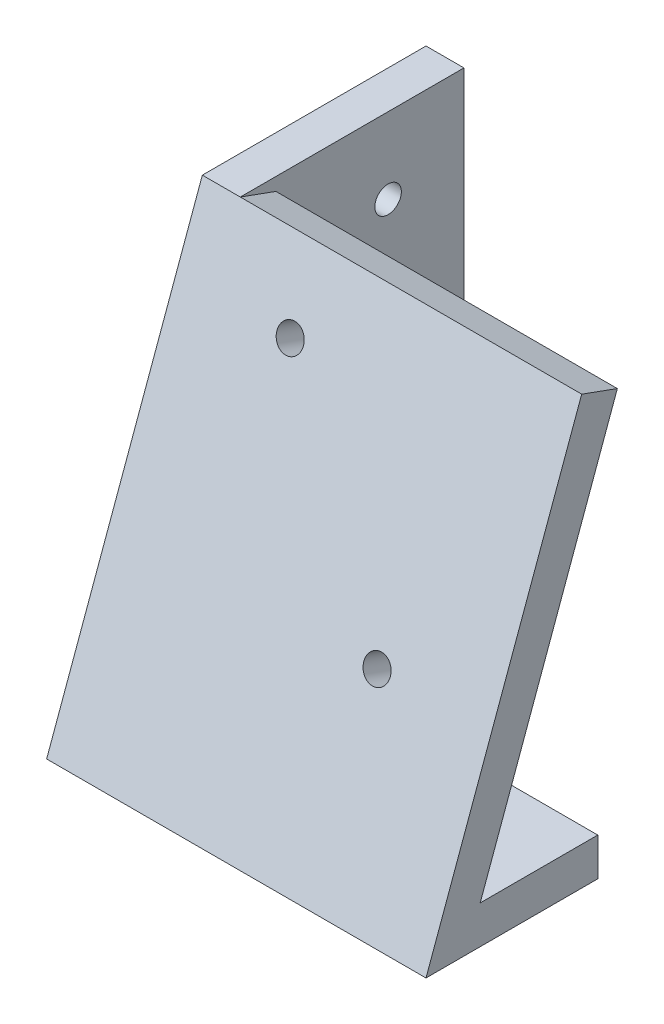
SolidWorks part; units mm, degrees
material "ABS"
ref_plane "Front Plane" through (0, 0, 0) normal (0, 0, 1) x (1, 0, 0)
ref_plane "Top Plane" through (0, 0, 0) normal (0, 1, 0) x (1, 0, 0)
ref_plane "Right Plane" through (0, 0, 0) normal (1, 0, 0) x (0, 0, -1)
sketch "Sketch1" plane through (0, 0, 0) normal (1, 0, 0) x (0, 0, -1)
  line L0 (0, 0) -> (-50, 0)
  line L1 (-50, 0) -> (-29.4788, 56.3816)
  line L2 (-29.4788, 56.3816) -> (-24.7803, 54.6715)
  line L3 (-24.7803, 54.6715) -> (-42.8593, 5)
  line L4 (-42.8593, 5) -> (0, 5)
  line L5 (0, 5) -> (0, 0)
  dimension "D1" = 60
  dimension "D2" = 50
  dimension "D3" = 70
  dimension "D4" = 5
  dimension "D5" = 5
extrude "Main" add sketch "Sketch1" along normal mid plane 50
sketch "Sketch2" plane through (0, 0, 0) normal (0, 0, -1) x (-1, 0, 0)
  line L0 (-25, 56.3816) -> (25, 56.3816) construction
  line L1 (-25, 0) -> (-20, 0)
  line L2 (-25, 0) -> (-25, 56.3816)
  line L3 (-25, 56.3816) -> (-20, 56.3816)
  line L4 (-20, 0) -> (-20, 56.3816)
  dimension "D1" = 5
extrude "Back" add sketch "Sketch2" against normal up to next
hole_wizard "Base Holes" positions "3DSketch4" profile "Sketch5" hole size "Ø3.5" standard "ANSI Metric"
sketch3d "3DSketch4"
  line L0 (-25, 5, 0) -> (-25, 5, 42.8593) construction
  line L4 (20, 5, 42.8593) -> (-25, 5, 42.8593) construction
  point P0 (10, 5, 32.6993)
  point P2 (-10, 5, 32.6993)
  dimension "D1" = 15
  dimension "D2" = 15
  dimension "D3" = 10.16
  dimension "D4" = 10.16
sketch "Sketch5" plane through (10, 5, 32.6993) normal (1, 0, 0) x (0, 0, 1)
  line L0 (0, 0) -> (0, 5)
  line L1 (0, 5) -> (1.75, 5)
  line L2 (1.75, 5) -> (1.75, 0)
  line L5 (1.75, 0) -> (0, 0)
  line L10 (0, 5) -> (-1.75, 5) construction
  line L11 (0, -6.35) -> (0, 107.95) construction
  dimension "Hole Dia." = 3.5
  dimension "Hole Depth" = 5
  dimension "Drill Angle" = 180
hole_wizard "BackPanelHoles" positions "Sketch6" profile "Sketch7" hole size "Ø1.0" standard "ANSI Metric"
sketch "Sketch6" plane through (20, 0, 0) normal (-1, 0, 0) x (0, 0, 1)
  line L0 (29.4788, 56.3816) -> (0, 56.3816) construction
  line L1 (0, 5) -> (0, 56.3816) construction
  line L2 (50, 0) -> (0, 0) construction
  point P0 (10, 46.3816)
  point P2 (25, 20)
  dimension "D1" = 10
  dimension "D2" = 10
  dimension "D3" = 20
  dimension "D4" = 25
sketch "Sketch7" plane through (20, 46.3816, 10) normal (0, 1, 0) x (0, 0, 1)
  line L0 (0, 0) -> (0, 5)
  line L1 (0, 5) -> (1.75, 5)
  line L2 (1.75, 5) -> (1.75, 0)
  line L5 (1.75, 0) -> (0, 0)
  line L10 (0, 5) -> (-1.75, 5) construction
  line L11 (0, -6.35) -> (0, 107.95) construction
  dimension "Hole Dia." = 3.5
  dimension "Hole Depth" = 5
  dimension "Drill Angle" = 180
hole_wizard "Ø1.0mm Dowel Hole1" positions "3DSketch5" profile "Sketch8" hole size "Ø1.0" standard "ANSI Metric"
sketch3d "3DSketch5"
  line L1 (20, 56.3816, 29.4788) -> (-25, 56.3816, 29.4788) construction
  line L2 (25, 0, 50) -> (-25, 0, 50) construction
  line L3 (-25, 56.3816, 29.4788) -> (-25, 0, 50) construction
  line L4 (25, 56.3816, 29.4788) -> (25, 0, 50) construction
  point P0 (-10, 46.9846, 32.899)
  point P2 (10, 23.4923, 41.4495)
  dimension "D1" = 15
  dimension "D2" = 10
  dimension "D3" = 25
  dimension "D4" = 15
sketch "Sketch8" plane through (-10, 46.9846, 32.899) normal (1, 0, 0) x (0, -0.9397, 0.342)
  line L0 (0, 0) -> (0, 5)
  line L1 (0, 5) -> (1.75, 5)
  line L2 (1.75, 5) -> (1.75, 0)
  line L5 (1.75, 0) -> (0, 0)
  line L10 (0, 5) -> (-1.75, 5) construction
  line L11 (0, -6.35) -> (0, 107.95) construction
  dimension "Hole Dia." = 3.5
  dimension "Hole Depth" = 5
  dimension "Drill Angle" = 180
ref_plane "Midplane" through (0, 0, 0) normal (-1, 0, 0) x (0, 0, 1)
mirror "Mirror1" about plane through (0, 0, 0) normal (-1, 0, 0) of "BackPanelHoles", "Back"
sketch "Sketch9" plane through (20, 0, 0) normal (-1, 0, 0) x (0, 0, 1)
  line L0 (29.4788, 56.3816) -> (0, 56.3816)
  line L1 (0, 56.3816) -> (0, 5)
  line L2 (0, 5) -> (42.8593, 5)
  line L3 (42.8593, 5) -> (24.7803, 54.6715)
  line L4 (24.7803, 54.6715) -> (29.4788, 56.3816)
extrude "Mirror Cut" cut sketch "Sketch9" against normal up to next
sketch "Sketch10" plane through (0, 5, 0) normal (0, 1, 0) x (1, 0, 0)
  line L0 (25, -42.8593) -> (25, 0) construction
  line L1 (-20, 0) -> (25, 0)
  line L2 (-20, 0) -> (-20, -5)
  line L3 (-20, -5) -> (25, -5)
  line L4 (25, 0) -> (25, -5)
  dimension "D1" = 5
extrude "BatteryCut" cut sketch "Sketch10" against normal up to next
sketch "Sketch11" plane through (0, 5, 0) normal (0, 1, 0) x (1, 0, 0)
  line L0 (-20, -5) -> (25, -5) construction
  line L1 (-8.3622, -5) -> (25, -5)
  line L2 (-8.3622, -5) -> (-8.3622, -27.3622)
  line L3 (-8.3622, -27.3622) -> (25, -27.3622)
  line L4 (25, -5) -> (25, -27.3622)
  line L5 (3.6378, -27.3622) -> (-7.3622, -27.3622) construction
  line L6 (-7.3622, -27.3622) -> (-7.3622, -11.3622) construction
  line L8 (25, -42.8593) -> (25, -5) construction
  dimension "D1" = 1
extrude "Cut-Extrude1" cut sketch "Sketch11" against normal through all
